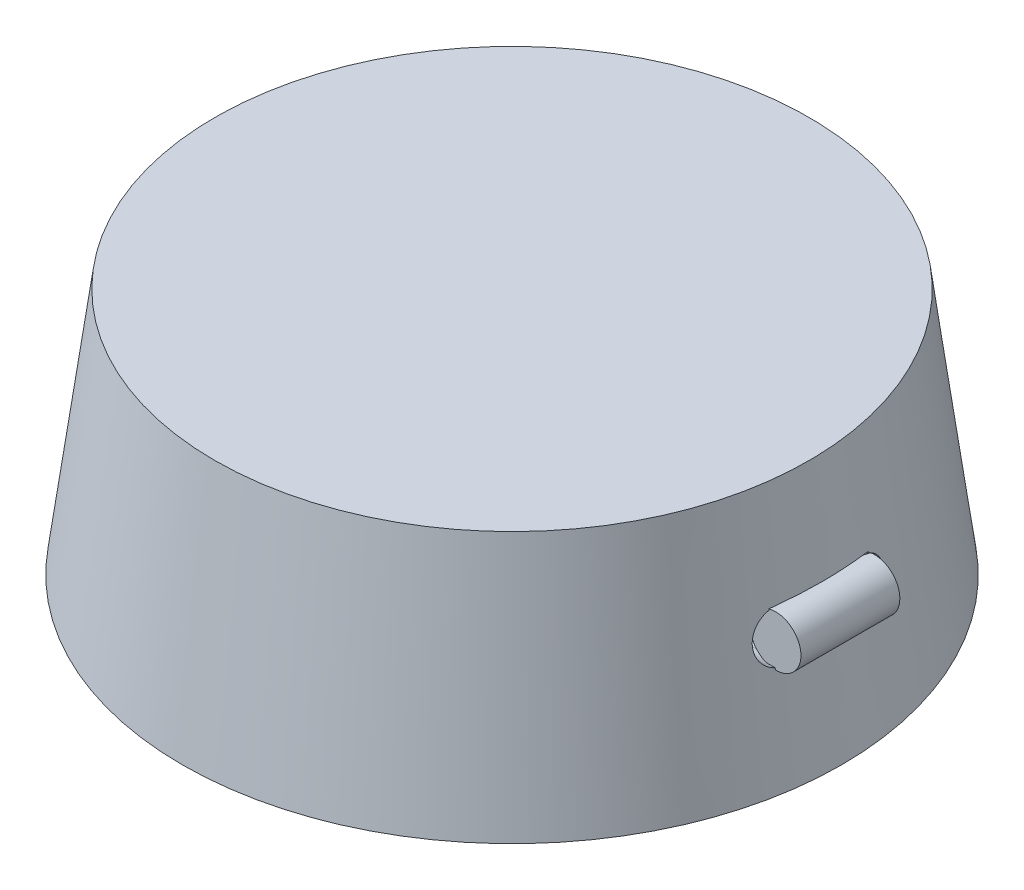
SolidWorks part; units mm, degrees
material "5052-O"
ref_plane "Front Plane" through (0, 0, 0) normal (0, 0, 1) x (1, 0, 0)
ref_plane "Top Plane" through (0, 0, 0) normal (0, 1, 0) x (1, 0, 0)
ref_plane "Right Plane" through (0, 0, 0) normal (1, 0, 0) x (0, 0, -1)
sketch "Sketch1" plane through (0, 0, 0) normal (0, 1, 0) x (1, 0, 0)
  circle A0 centre (0, 0) radius 100
  dimension "D1" = 200
extrude "Boss-Extrude1" add sketch "Sketch1" along normal blind 75 draft 7.5
sketch "Sketch2" plane through (0, 0, 0) normal (1, 0, 0) x (0, 0, -1)
  line L0 (-12.5278, 37.5) -> (12.4722, 37.5) construction
  line L1 (-12.5278, 45) -> (12.4722, 45)
  line L2 (-12.5278, 30) -> (12.4722, 30)
  arc A0 (-12.5278, 45) -> (-12.5278, 30) centre (-12.5278, 37.5) ccw
  arc A1 (12.4722, 30) -> (12.4722, 45) centre (12.4722, 37.5) ccw
  point P2 (-0.0278, 37.5)
  dimension "D1" = 15
  dimension "D2" = 25
  dimension "D3" = 37.5
extrude "Cut-Extrude1" cut sketch "Sketch2" against normal blind 122 and the other way blind 125
sketch "Sketch3" plane through (0, 0, 0) normal (0, 0, 1) x (1, 0, 0)
  circle A0 centre (94.9606, 37.5261) radius 7.6732
extrude "Boss-Extrude5" add sketch "Sketch3" along normal blind 15 and the other way blind 15
mirror "Mirror1" about plane through (0, 0, 0) normal (1, 0, 0) of "Boss-Extrude5"
sketch "Sketch5" plane through (0, 0, 0) normal (0, -1, 0) x (1, 0, 0)
  circle A0 centre (0, 0) radius 25
  dimension "D1" = 50
extrude "Cut-Extrude3" cut sketch "Sketch5" against normal blind 12.5
ref_plane "Plane1" through (0, 12.5, 0) normal (0, 1, 0) x (1, 0, 0)
sketch "Sketch6" plane through (0, 12.5, 0) normal (0, 1, 0) x (1, 0, 0)
  circle A0 centre (0, 0) radius 62.5
  dimension "D1" = 125
extrude "Cut-Extrude4" cut sketch "Sketch6" along normal blind 22.5
